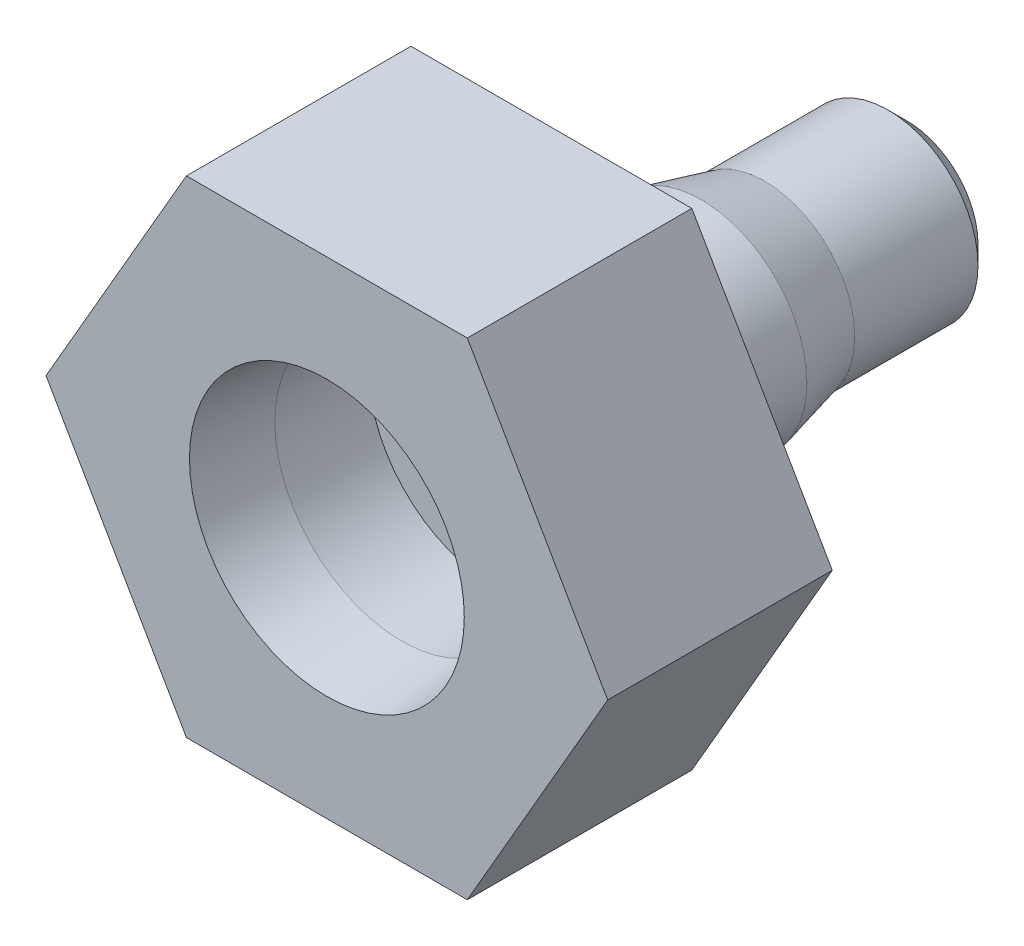
SolidWorks part; units mm, degrees
ref_plane "Front Plane" through (0, 0, 0) normal (0, 0, 1) x (1, 0, 0)
ref_plane "Top Plane" through (0, 0, 0) normal (0, 1, 0) x (1, 0, 0)
ref_plane "Right Plane" through (0, 0, 0) normal (1, 0, 0) x (0, 0, -1)
sketch "Sketch1" plane through (0, 0, 0) normal (0, 0, 1) x (1, 0, 0)
  circle A0 centre (0, 0) radius 2.825
  dimension "D1" = 5.65
extrude "Boss-Extrude1" add sketch "Sketch1" along normal blind 9.5
sketch "Sketch2" plane through (0, 0, 9.5) normal (0, 0, 1) x (1, 0, 0)
  circle A0 centre (0, 0) radius 6.5
  dimension "D1" = 13
extrude "Boss-Extrude2" add sketch "Sketch2" along normal blind 6 contours A0
sketch "Sketch3" plane through (0, 0, 15.5) normal (0, 0, 1) x (1, 0, 0)
  circle A0 centre (0, 0) radius 0.85
  dimension "D1" = 1.7
extrude "Cut-Extrude1" cut sketch "Sketch3" against normal up to surface (15.5 mm away) up to face at (2.825, 0, 0)
sketch "Sketch4" plane through (0, 0, 15.5) normal (0, 0, 1) x (1, 0, 0)
  circle A0 centre (0, 0) radius 2.5
  dimension "D1" = 5
extrude "Cut-Extrude2" cut sketch "Sketch4" against normal blind 4
chamfer "Chamfer1" distance 1 angle 45 1 edges at (2.825, 0, 9.5)
sketch "Sketch10" plane through (0, 0, 15.5) normal (0, 0, 1) x (1, 0, 0)
  line L1 (3.7528, 6.5) -> (-3.7528, 6.5)
  line L2 (-3.7528, 6.5) -> (-7.5056, 0)
  line L3 (-7.5056, 0) -> (-3.7528, -6.5)
  line L4 (-3.7528, -6.5) -> (3.7528, -6.5)
  line L5 (3.7528, -6.5) -> (7.5056, 0)
  line L6 (7.5056, 0) -> (3.7528, 6.5)
  circle A0 centre (0, 0) radius 11.55 construction
  circle A1 centre (0, 0) radius 0.85
  circle A2 centre (0, 0) radius 6.5 construction
  circle A3 centre (0, 0) radius 0.85 construction
extrude "Boss-Extrude5" add sketch "Sketch10" against normal up to surface (6 mm away) up to face at (3.825, 0, 9.5)
sketch "Sketch11" plane through (0, 0, 0) normal (0, 0, -1) x (-1, 0, 0)
  circle A0 centre (0, 0) radius 2.825
  circle A1 centre (0, 0) radius 2.825 construction
  circle A2 centre (0, 0) radius 2.4
  dimension "D1" = 4.8
extrude "Cut-Extrude3" cut sketch "Sketch11" against normal offset from surface (6 mm away) 3.5 up to face at (3.825, 0, 9.5)
chamfer "Chamfer2" distance 0.55 angle 76 1 edges at (2.4, 0, 6) first distance on face at (2.825, 0, 6)
chamfer "Chamfer3" distance 0.5 angle 45 1 edges at (-2.4, 0, 0)
sketch "Sketch12" plane through (0, 0, 15.5) normal (0, 0, 1) x (1, 0, 0)
  circle A0 centre (0, 0) radius 3.3909
  dimension "D1" = 6.7818
extrude "Cut-Extrude4" cut sketch "Sketch12" against normal blind 4.5
chamfer "Chamfer4" distance 2 angle 8 1 edges at (3.3909, 0, 15.5) first distance on face at (3.3909, 0, 11)
